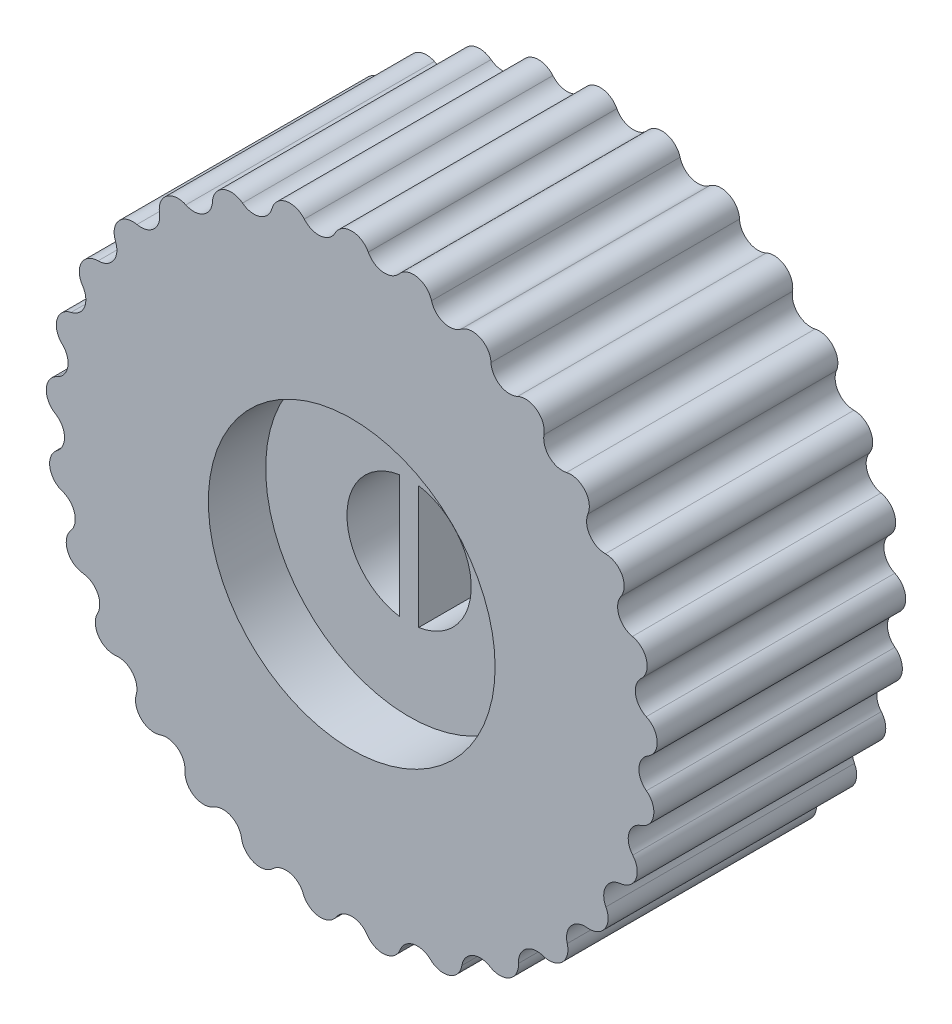
SolidWorks part; units mm, degrees
ref_plane "Front Plane" through (0, 0, 0) normal (0, 0, 1) x (1, 0, 0)
ref_plane "Top Plane" through (0, 0, 0) normal (0, 1, 0) x (1, 0, 0)
ref_plane "Right Plane" through (0, 0, 0) normal (1, 0, 0) x (0, 0, -1)
sketch "Sketch1" plane through (0, 0, 0) normal (0, 0, 1) x (1, 0, 0)
  line L0 (0, 0) -> (0, 16) construction
  circle A0 centre (0, 0) radius 16 construction
  circle A1 centre (0, 0) radius 15.5 construction
  arc A2 (-0.8662, 15.4758) -> (0.8662, 15.4758) centre (0, 15.0222) cw
  arc A3 (0.8662, 15.4758) -> (2.4809, 15.3002) centre (1.7324, 15.9293) ccw
  arc A4 (4.1728, 14.9278) -> (5.712, 14.4091) centre (5.1162, 15.1845) ccw
  arc A5 (2.4809, 15.3002) -> (4.1728, 14.9278) centre (3.2293, 14.671) cw
  arc A6 (7.2843, 13.6817) -> (8.676, 12.8444) centre (8.2608, 13.7296) ccw
  arc A7 (5.712, 14.4091) -> (7.2843, 13.6817) centre (6.3077, 13.6338) cw
  arc A8 (10.0551, 11.796) -> (11.2343, 10.679) centre (11.0192, 11.6328) ccw
  arc A9 (8.676, 12.8444) -> (10.0551, 11.796) centre (9.0911, 11.9591) cw
  arc A10 (12.3558, 9.3586) -> (13.2673, 8.0143) centre (13.2623, 8.992) ccw
  arc A11 (11.2343, 10.679) -> (12.3558, 9.3586) centre (11.4494, 9.7252) cw
  arc A12 (14.0788, 6.4837) -> (14.6799, 4.9748) centre (14.8852, 5.9308) ccw
  arc A13 (13.2673, 8.0143) -> (14.0788, 6.4837) centre (13.2723, 7.0365) cw
  arc A14 (15.1434, 3.3056) -> (15.4062, 1.7028) centre (15.8122, 2.5923) ccw
  arc A15 (14.6799, 4.9748) -> (15.1434, 3.3056) centre (14.4747, 4.0189) cw
  arc A16 (15.5, -0.0271) -> (15.412, -1.6489) centre (15.9997, -0.8675) ccw
  arc A17 (15.4062, 1.7028) -> (15.5, -0.0271) centre (15.0002, 0.8133) cw
  arc A18 (15.1318, -3.3585) -> (14.6973, -4.9235) centre (15.4392, -4.2867) ccw
  arc A19 (15.412, -1.6489) -> (15.1318, -3.3585) centre (14.8243, -2.4303) cw
  arc A20 (14.056, -6.5329) -> (13.2952, -7.9679) centre (14.1567, -7.5054) ccw
  arc A21 (14.6973, -4.9235) -> (14.056, -6.5329) centre (13.9553, -5.5603) cw
  arc A22 (12.323, -9.4018) -> (11.2715, -10.6397) centre (12.2123, -10.3732) ccw
  arc A23 (13.2952, -7.9679) -> (12.323, -9.4018) centre (12.4337, -8.4303) cw
  arc A24 (10.0138, -11.831) -> (8.7208, -12.814) centre (9.6969, -12.756) ccw
  arc A25 (11.2715, -10.6397) -> (10.0138, -11.831) centre (10.3308, -10.9061) cw
  arc A26 (7.2364, -13.7071) -> (5.7623, -14.3891) centre (6.728, -14.5423) ccw
  arc A27 (8.7208, -12.814) -> (7.2364, -13.7071) centre (7.7448, -12.8719) cw
  arc A28 (4.1206, -14.9423) -> (2.5344, -15.2914) centre (3.4445, -15.6486) ccw
  arc A29 (5.7623, -14.3891) -> (4.1206, -14.9423) centre (4.7966, -14.2359) cw
  arc A30 (0.8121, -15.4787) -> (-0.8121, -15.4787) centre (0, -16.0232) ccw
  arc A31 (2.5344, -15.2914) -> (0.8121, -15.4787) centre (1.6242, -14.9342) cw
  arc A32 (-2.5344, -15.2914) -> (-4.1206, -14.9423) centre (-3.4445, -15.6486) ccw
  arc A33 (-0.8121, -15.4787) -> (-2.5344, -15.2914) centre (-1.6242, -14.9342) cw
  arc A34 (-5.7623, -14.3891) -> (-7.2364, -13.7071) centre (-6.728, -14.5423) ccw
  arc A35 (-4.1206, -14.9423) -> (-5.7623, -14.3891) centre (-4.7966, -14.2359) cw
  arc A36 (-8.7208, -12.814) -> (-10.0138, -11.831) centre (-9.6969, -12.756) ccw
  arc A37 (-7.2364, -13.7071) -> (-8.7208, -12.814) centre (-7.7448, -12.8719) cw
  arc A38 (-11.2715, -10.6397) -> (-12.323, -9.4018) centre (-12.2123, -10.3732) ccw
  arc A39 (-10.0138, -11.831) -> (-11.2715, -10.6397) centre (-10.3308, -10.9061) cw
  arc A40 (-13.2952, -7.9679) -> (-14.056, -6.5329) centre (-14.1567, -7.5054) ccw
  arc A41 (-12.323, -9.4018) -> (-13.2952, -7.9679) centre (-12.4337, -8.4303) cw
  arc A42 (-14.6973, -4.9235) -> (-15.1318, -3.3585) centre (-15.4392, -4.2867) ccw
  arc A43 (-14.056, -6.5329) -> (-14.6973, -4.9235) centre (-13.9553, -5.5603) cw
  arc A44 (-15.412, -1.6489) -> (-15.5, -0.0271) centre (-15.9997, -0.8675) ccw
  arc A45 (-15.1318, -3.3585) -> (-15.412, -1.6489) centre (-14.8243, -2.4303) cw
  arc A46 (-15.4062, 1.7028) -> (-15.1434, 3.3056) centre (-15.8122, 2.5923) ccw
  arc A47 (-15.5, -0.0271) -> (-15.4062, 1.7028) centre (-15.0002, 0.8133) cw
  arc A48 (-14.6799, 4.9748) -> (-14.0788, 6.4837) centre (-14.8852, 5.9308) ccw
  arc A49 (-15.1434, 3.3056) -> (-14.6799, 4.9748) centre (-14.4747, 4.0189) cw
  arc A50 (-13.2673, 8.0143) -> (-12.3558, 9.3586) centre (-13.2623, 8.992) ccw
  arc A51 (-14.0788, 6.4837) -> (-13.2673, 8.0143) centre (-13.2723, 7.0365) cw
  arc A52 (-11.2343, 10.679) -> (-10.0551, 11.796) centre (-11.0192, 11.6328) ccw
  arc A53 (-12.3558, 9.3586) -> (-11.2343, 10.679) centre (-11.4494, 9.7252) cw
  arc A54 (-8.676, 12.8444) -> (-7.2843, 13.6817) centre (-8.2608, 13.7296) ccw
  arc A55 (-10.0551, 11.796) -> (-8.676, 12.8444) centre (-9.0911, 11.9591) cw
  arc A56 (-5.712, 14.4091) -> (-4.1728, 14.9278) centre (-5.1162, 15.1845) ccw
  arc A57 (-7.2843, 13.6817) -> (-5.712, 14.4091) centre (-6.3077, 13.6338) cw
  arc A58 (-2.4809, 15.3002) -> (-0.8662, 15.4758) centre (-1.7324, 15.9293) ccw
  arc A59 (-4.1728, 14.9278) -> (-2.4809, 15.3002) centre (-3.2293, 14.671) cw
  point P152 (0, 0)
  dimension "D1" = 32
  dimension "D2" = 0.5
  dimension "D3" = 29
extrude "Boss-Extrude1" add sketch "Sketch1" along normal blind 13
sketch "Sketch4" plane through (0, 0, 13) normal (0, 0, 1) x (1, 0, 0)
  circle A0 centre (0, 0) radius 3.25
  dimension "D1" = 6.5
extrude "Cut-Extrude1" cut sketch "Sketch4" against normal blind 12
sketch "Sketch5" plane through (0, 0, 13) normal (0, 0, 1) x (1, 0, 0)
  circle A0 centre (0, 0) radius 7.5
  dimension "D1" = 15
extrude "Cut-Extrude2" cut sketch "Sketch5" against normal blind 3
sketch "Sketch6" plane through (0, 0, 1) normal (0, 0, 1) x (1, 0, 0)
  line L1 (-0.5, -3.4543) -> (0.5, -3.4543)
  line L2 (-0.5, -3.4543) -> (-0.5, 3.4543)
  line L3 (-0.5, 3.4543) -> (0.5, 3.4543)
  line L4 (0.5, -3.4543) -> (0.5, 3.4543)
  line L5 (-0.5, -3.4543) -> (0.5, 3.4543) construction
  line L6 (-0.5, 3.4543) -> (0.5, -3.4543) construction
  point P0 (0, 0)
  dimension "D1" = 1
extrude "Boss-Extrude4" add sketch "Sketch6" along normal up to surface (9 mm away) up to face at (7.5, 0, 10)
fillet "Fillet1" radius 1 4 edges at (3.25, 0, 1) (-3.25, 0, 1) (-0.5, 0, 1) (0.5, 0, 1)
